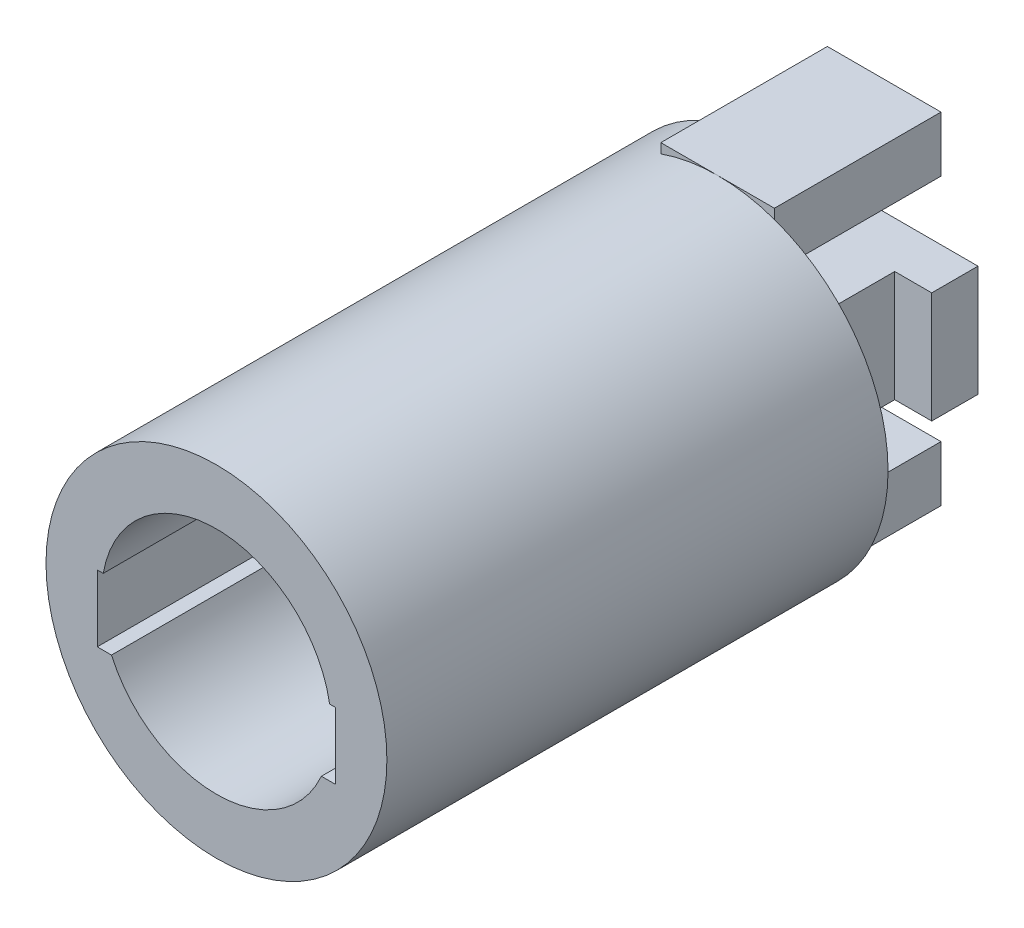
SolidWorks part; units mm, degrees
ref_plane "Front Plane" through (0, 0, 0) normal (0, 0, 1) x (1, 0, 0)
ref_plane "Top Plane" through (0, 0, 0) normal (0, 1, 0) x (1, 0, 0)
ref_plane "Right Plane" through (0, 0, 0) normal (1, 0, 0) x (0, 0, -1)
ref_plane "Plane6" through (0, 0, 0) normal (0, 0, 1) x (1, 0, 0)
sketch "Sketch9" plane through (0, 0, 0) normal (0, 0, 1) x (1, 0, 0)
  line L0 (17.9123, -8.844) -> (17.9123, 0.366)
  line L1 (21.1323, -4.604) -> (14.6923, -4.604) construction
  line L5 (14.6923, -3.704) -> (21.1323, -3.704)
  line L6 (14.6923, -3.704) -> (14.6923, -5.504)
  line L7 (14.6923, -5.504) -> (21.1323, -5.504)
  line L8 (21.1323, -3.704) -> (21.1323, -5.504)
  line L10 (17.9123, -5.504) -> (17.9123, -3.704) construction
  circle A0 centre (17.9123, -4.239) radius 4.605
  circle A1 centre (17.9123, -4.239) radius 3.105
  point P4 (0, 0)
  point P5 (0, 0)
  point P6 (17.9123, -12.5328)
  point P9 (17.9123, -4.604)
  dimension "D1" = 6.21
  dimension "D8" = 1.5
  dimension "D3" = 0.9
  dimension "D4" = 0.9
  dimension "D6" = 3.22
  dimension "D7" = 3.22
ref_plane "Plane8" through (0, 0, -13.54) normal (0, 0, 1) x (1, 0, 0)
extrude "Boss-Extrude6" add sketch "Sketch9" against normal up to surface (13.54 mm away) contours A0 A1 L5 L8 L7 L6 | A1 L5 L8 L7 L0 A0 region at (13.4102, -4.239, 0) region at (18.0152, -8.094, 0) up to plane "Plane8"
extrude "Boss-Extrude9" add sketch "Sketch9<8>" against normal blind 1.5 from surface contours A1 L0 A0 L7 L6 L5 | L7 A1 L0 | L5 A1 L7 L0 | L0 A1 L5 | A1 L5 L6 L7 region at (13.4102, -4.239, 0) region at (16.7892, -6.2627, 0) region at (16.3921, -4.5932, 0) region at (14.7986, -4.7849, 0) region at (16.6579, -2.6277, 0) starting at plane "Plane8"
sketch "Sketch9<8>" plane through (0, 0, 0) normal (0, 0, 1) x (1, 0, 0) same geometry as "Sketch9"
ref_plane "Plane10" through (0, 0, -15.04) normal (0, 0, -1) x (-1, 0, 0)
sketch "Sketch11" plane through (0, 0, -13.54) normal (0, 0, 1) x (1, 0, 0)
  line L1 (16.3773, -8.844) -> (19.4473, -8.844)
  line L2 (16.3773, -8.844) -> (16.3773, 0.366)
  line L3 (16.3773, 0.366) -> (19.4473, 0.366)
  line L4 (19.4473, -8.844) -> (19.4473, 0.366)
  line L5 (16.3773, -8.844) -> (19.4473, 0.366) construction
  line L6 (16.3773, 0.366) -> (19.4473, -8.844) construction
  line L8 (15.3773, -5.739) -> (20.4473, -5.739)
  line L9 (15.3773, -5.739) -> (15.3773, -2.739)
  line L10 (15.3773, -2.739) -> (20.4473, -2.739)
  line L11 (20.4473, -5.739) -> (20.4473, -2.739)
  line L12 (15.3773, -5.739) -> (20.4473, -2.739) construction
  line L13 (15.3773, -2.739) -> (20.4473, -5.739) construction
  line L14 (19.4473, -1.134) -> (16.3773, -1.134)
  line L15 (19.4473, -7.344) -> (16.3773, -7.344)
  arc A1 (20.9708, -3.704) -> (17.9123, -1.134) centre (17.9123, -4.239) ccw construction
  arc A2 (17.9123, -7.344) -> (20.7479, -5.504) centre (17.9123, -4.239) ccw construction
  point P0 (17.9123, -4.239)
  point P9 (17.9123, -4.239)
  dimension "D1" = 3.07
  dimension "D2" = 3
  dimension "D3" = 1
extrude "Boss-Extrude7" add sketch "Sketch11" against normal blind 3 and the other way blind 1.5 from surface contours L14 L4 L3 L2 | L4 L15 L2 L1 | L10 L2 L8 L4 region at (17.9123, -8.094, -13.54) region at (17.9123, -4.239, -13.54) region at (17.9123, -0.384, -13.54) starting at plane "Plane10"
ref_plane "Plane11" through (0, 0, -18.04) normal (0, 0, -1) x (-1, 0, 0)
extrude "Boss-Extrude10" add sketch "Sketch11<8>" along normal blind 1.25 from surface contours L10 L9 L8 L2 | L8 L11 L10 L4 region at (15.8773, -4.239, -13.54) region at (19.9473, -4.239, -13.54) starting at plane "Plane11"
sketch "Sketch11<8>" plane through (0, 0, -13.54) normal (0, 0, 1) x (1, 0, 0) same geometry as "Sketch11"
equation "\"D1@Boss-Extrude10\"=1.50mm-.25"
